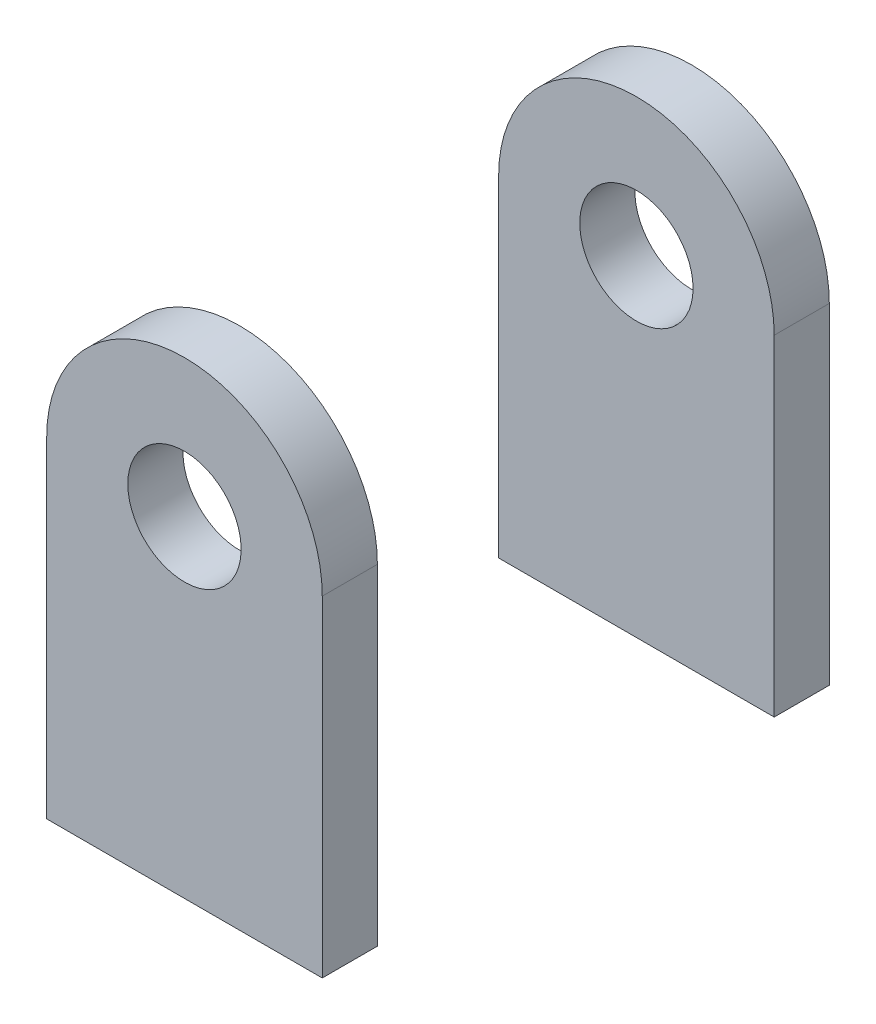
SolidWorks part; units mm, degrees
material "AISI 4130 Steel, normalized at 870C"
ref_plane "Front Plane" through (0, 0, 0) normal (0, 0, 1) x (1, 0, 0)
ref_plane "Top Plane" through (0, 0, 0) normal (0, 1, 0) x (1, 0, 0)
ref_plane "Right Plane" through (0, 0, 0) normal (1, 0, 0) x (0, 0, -1)
sketch "Sketch1" plane through (0, 0, 0) normal (0, 0, 1) x (1, 0, 0)
  line L0 (7.9375, 0) -> (7.9375, -19.05)
  line L1 (7.9375, -19.05) -> (-7.9375, -19.05)
  line L2 (-7.9375, -19.05) -> (-7.9375, 0)
  line L3 (0, 0) -> (0, -19.05) construction
  circle A0 centre (0, 0) radius 3.2639
  circle A1 centre (0, 0) radius 7.9375
  dimension "D1" = 6.5278
  dimension "D2" = 15.875
  dimension "D3" = 19.05
extrude "Boss-Extrude1" add sketch "Sketch1" along normal blind 3.175 from offset 11.43 contours A1 A0 | A1 L2 L1 L0 | L3 A1 L2 L1 region at (5.4539, -5.4539, 0) region at (4.2606, -12.5196, 0) region at (-4.2606, -12.5196, 0)
extrude "Boss-Extrude2" add sketch "Sketch1<4>" against normal blind 3.175 from offset 11.43 separate body contours A1 A0 | A1 L2 L1 L0 | L3 A1 L2 L1 region at (5.4539, -5.4539, 0) region at (4.2606, -12.5196, 0) region at (-4.2606, -12.5196, 0) offset against normal yes
sketch "Sketch1<4>" plane through (0, 0, 0) normal (0, 0, 1) x (1, 0, 0) same geometry as "Sketch1"
equation "\"Width Between Tabs\"= .9"
equation "\"Tab Thickness\"= 1 / 8"
equation "\"D19@Boss-Extrude1\"=\"Width Between Tabs\"/2"
equation "\"D1@Boss-Extrude1\"=\"Tab Thickness\""
equation "\"D19@Boss-Extrude2\"=\"Width Between Tabs\"/2"
equation "\"D1@Boss-Extrude2\"=\"Tab Thickness\""
equation "\"Hole Diameter\"= .257"
equation "\"D1@Sketch1\"=\"Hole Diameter\""
